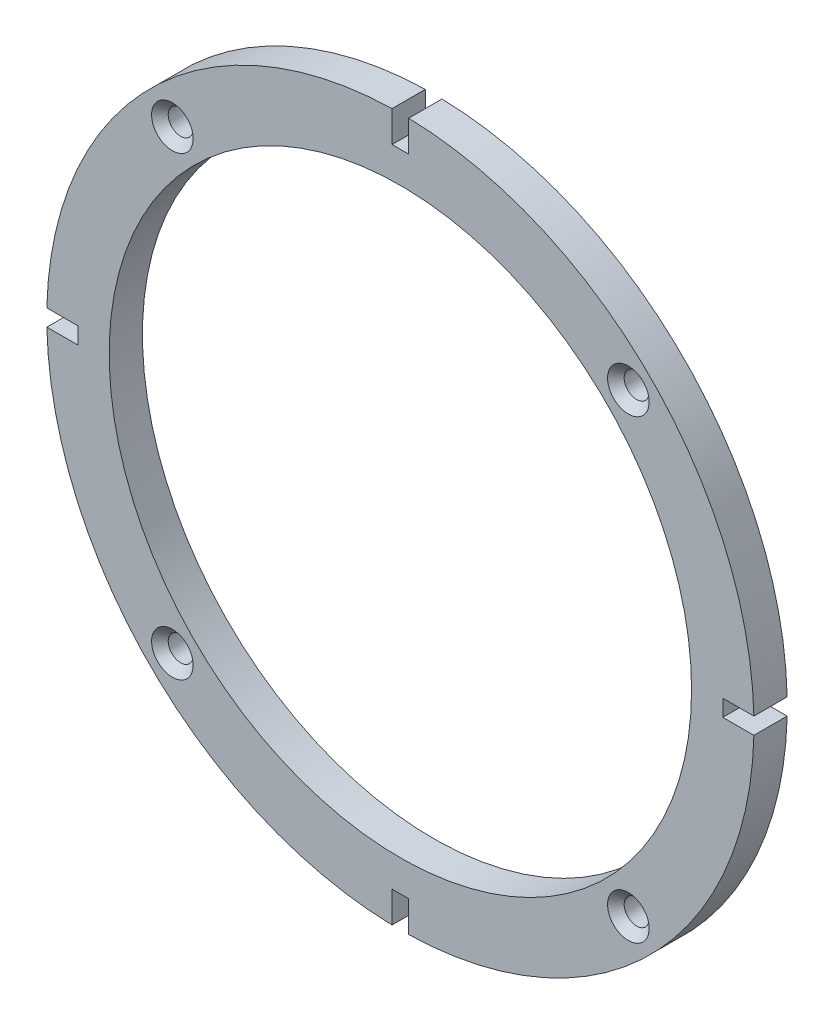
SolidWorks part; units mm, degrees
material "Stop 1060"
ref_plane "Płaszczyzna przednia" through (0, 0, 0) normal (0, 0, 1) x (1, 0, 0)
ref_plane "Płaszczyzna górna" through (0, 0, 0) normal (0, 1, 0) x (1, 0, 0)
ref_plane "Płaszczyzna prawa" through (0, 0, 0) normal (1, 0, 0) x (0, 0, -1)
sketch "Sketch1" plane through (0, 0, 0) normal (0, 0, 1) x (1, 0, 0)
  line L0 (84.9765, -2) -> (77.4996, -2)
  line L1 (-2, 77.4996) -> (2, 77.4996)
  line L2 (-2, 77.4996) -> (-2, 84.9765)
  line L4 (2, 84.9765) -> (2, 77.4996)
  line L5 (77.4996, 2) -> (84.9765, 2)
  line L6 (77.4996, 2) -> (77.4996, -2)
  line L7 (-2, -84.9765) -> (-2, -77.4996)
  line L8 (2, -77.4996) -> (2, -84.9765)
  line L9 (2, -77.4996) -> (-2, -77.4996)
  line L10 (-84.9765, 2) -> (-77.4996, 2)
  line L11 (-77.4996, -2) -> (-84.9765, -2)
  line L12 (-77.4996, -2) -> (-77.4996, 2)
  circle A0 centre (0, 0) radius 70
  arc A1 (-2, 84.9765) -> (-84.9765, 2) centre (0, 0) ccw
  arc A2 (-84.9765, -2) -> (-2, -84.9765) centre (0, 0) ccw
  arc A3 (2, -84.9765) -> (84.9765, -2) centre (0, 0) ccw
  arc A4 (84.9765, 2) -> (2, 84.9765) centre (0, 0) ccw
  point P6 (-2, 77.4996)
  point P7 (2, 77.4996)
  point P24 (0, 0)
  dimension "D1" = 170
  dimension "D2" = 140
  dimension "D3" = 77.4996
  dimension "D4" = 2
  dimension "D5" = 4
  dimension "D6" = 4
extrude "Boss-Extrude1" add sketch "Sketch1" along normal blind 8 contours A0 | A1 L10 L12 L11 A2 L7 L9 L8 A3 L0 L6 L5 A4 L4 L1 L2 region at (0, 0, 0)
sketch "Sketch2" plane through (0, 0, 0) normal (0, 0, -1) x (-1, 0, 0)
  line L0 (0, 0) -> (-73.6832, 73.6832) construction
  line L1 (0, 0) -> (0, 118.1493) construction
  circle A0 centre (-54.8008, 54.8008) radius 3
  arc A1 (-2, 84.9765) -> (-84.9765, 2) centre (0, 0) ccw construction
  circle A2 centre (54.8008, 54.8008) radius 3
  circle A3 centre (54.8008, -54.8008) radius 3
  circle A4 centre (-54.8008, -54.8008) radius 3
  point P18 (0, 0)
  dimension "D3" = 6
  dimension "D1" = 77.5
  dimension "D2" = 45
  dimension "D4" = 4
extrude "Wytnij-wyciągnięcie1" cut sketch "Sketch2" against normal blind 10
sketch "Szkic1" plane through (0, 0, 0) normal (0, 0, -1) x (-1, 0, 0)
  circle A0 centre (-54.8008, 54.8008) radius 5
  dimension "D1" = 10
extrude "Wytnij-wyciągnięcie2" cut sketch "Szkic1" against normal blind 2 contours A0
pattern_circular "Szyk kołowy1" count 4 over 360 about axis through (0, 0, 8) along (0, 0, -1) of "Wytnij-wyciągnięcie2"
chamfer "Sfazowanie1" distance 2 4 edges at (57.8008, -54.8008, 8) (57.8008, 54.8008, 8) (-51.8008, 54.8008, 8) (-51.8008, -54.8008, 8)
